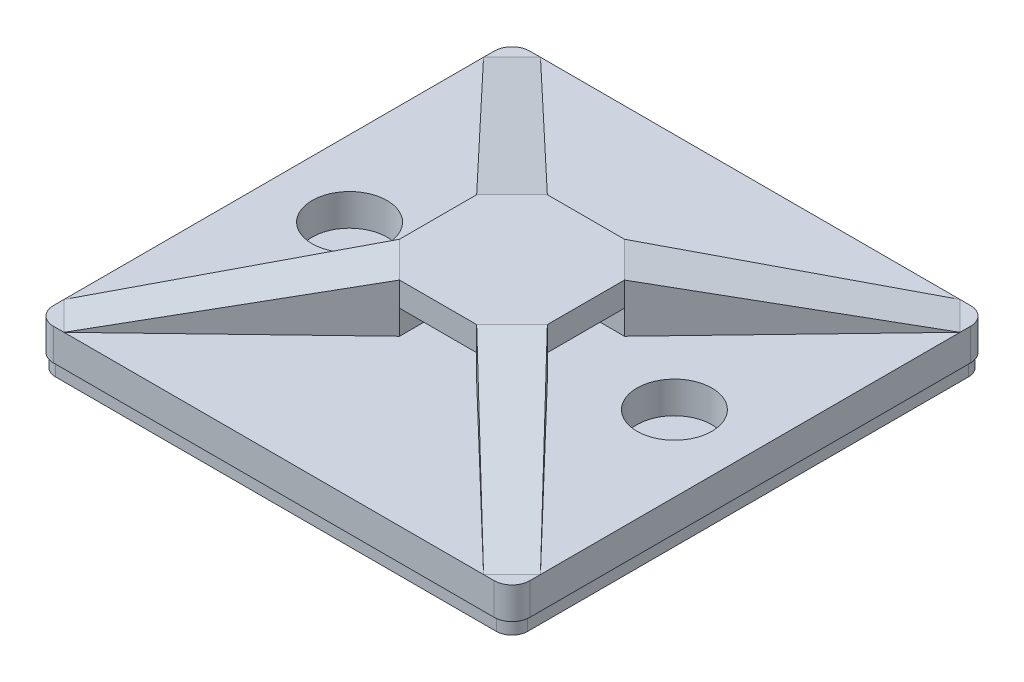
SolidWorks part; units mm, degrees
material "Nylon White"
ref_plane "Front Plane" through (0, 0, 0) normal (0, 0, 1) x (1, 0, 0)
ref_plane "Top Plane" through (0, 0, 0) normal (0, 1, 0) x (1, 0, 0)
ref_plane "Right Plane" through (0, 0, 0) normal (1, 0, 0) x (0, 0, -1)
sketch "Sketch1" plane through (0, 0, 0) normal (0, 1, 0) x (1, 0, 0)
  line L1 (13.2207, -14.2875) -> (-13.2207, -14.2875)
  line L2 (14.2875, -13.2207) -> (14.2875, 13.2207)
  line L3 (13.2207, 14.2875) -> (-13.2207, 14.2875)
  line L4 (-14.2875, -13.2207) -> (-14.2875, 13.2207)
  line L5 (14.2875, -14.2875) -> (-14.2875, 14.2875) construction
  line L6 (14.2875, 14.2875) -> (-14.2875, -14.2875) construction
  arc A0 (-14.2875, -13.2207) -> (-13.2207, -14.2875) centre (-13.2207, -13.2207) ccw
  arc A1 (14.2875, -13.2207) -> (13.2207, -14.2875) centre (13.2207, -13.2207) cw
  arc A2 (13.2207, 14.2875) -> (14.2875, 13.2207) centre (13.2207, 13.2207) cw
  arc A3 (-13.2207, 14.2875) -> (-14.2875, 13.2207) centre (-13.2207, 13.2207) ccw
  point P0 (0, 0)
  dimension "D2" = 1.0668
  dimension "D1" = 28.575
extrude "Boss-Extrude1" add sketch "Sketch1" along normal blind 1.905
sketch "Sketch2" plane through (0, 1.905, 0) normal (0, 1, 0) x (1, 0, 0)
  line L0 (-4.4323, 2.313) -> (-2.313, 4.4323) construction
  line L1 (4.4323, -2.313) -> (-4.4323, -2.313) construction
  line L2 (4.4323, -2.313) -> (4.4323, 2.313)
  line L3 (4.4323, 2.313) -> (-4.4323, 2.313) construction
  line L4 (-4.4323, -2.313) -> (-4.4323, 2.313)
  line L5 (4.4323, -2.313) -> (-4.4323, 2.313) construction
  line L6 (4.4323, 2.313) -> (-4.4323, -2.313) construction
  line L7 (2.313, -4.4323) -> (-2.313, -4.4323)
  line L8 (2.313, -4.4323) -> (2.313, 4.4323) construction
  line L9 (2.313, 4.4323) -> (-2.313, 4.4323)
  line L10 (-2.313, -4.4323) -> (-2.313, 4.4323) construction
  line L11 (2.313, -4.4323) -> (-2.313, 4.4323) construction
  line L12 (2.313, 4.4323) -> (-2.313, -4.4323) construction
  line L13 (2.313, 4.4323) -> (4.4323, 2.313) construction
  line L14 (4.4323, -2.313) -> (2.313, -4.4323) construction
  line L15 (-4.4323, -2.313) -> (-2.313, -4.4323) construction
  line L16 (-14.2875, 12.5813) -> (-12.5813, 14.2875)
  line L17 (-14.2875, 13.2207) -> (-14.2875, -13.2207) construction
  line L18 (13.2207, 14.2875) -> (-13.2207, 14.2875) construction
  line L19 (12.5813, 14.2875) -> (14.2875, 12.5813)
  line L20 (14.2875, -13.2207) -> (14.2875, 13.2207) construction
  line L21 (14.2875, -12.5813) -> (12.5813, -14.2875)
  line L22 (-13.2207, -14.2875) -> (13.2207, -14.2875) construction
  line L23 (-12.5813, -14.2875) -> (-14.2875, -12.5813)
  line L24 (-14.2875, 12.5813) -> (-4.4323, 2.313)
  line L25 (-12.5813, 14.2875) -> (-2.313, 4.4323)
  line L26 (2.313, 4.4323) -> (12.5813, 14.2875)
  line L27 (4.4323, 2.313) -> (14.2875, 12.5813)
  line L28 (4.4323, -2.313) -> (14.2875, -12.5813)
  line L29 (-4.4323, -2.313) -> (-14.2875, -12.5813)
  line L30 (-2.313, -4.4323) -> (-12.5813, -14.2875)
  line L31 (2.313, -4.4323) -> (12.5813, -14.2875)
  point P0 (0, 0)
  point P5 (0, 0)
  dimension "D1" = 8.8646
  dimension "D2" = 2.9972
  dimension "D3" = 2.413
extrude "Boss-Extrude2" add sketch "Sketch2" along normal blind 2.921
ref_axis "Axis1" through (0, 5.0673, 0) along (0, -1, 0)
ref_plane "Plane1" through (0, 0, 0) normal (0.7071, 0, 0.7071) x (0, -1, 0)
sketch "Sketch4" plane through (0, 0, 0) normal (0.7071, 0, 0.7071) x (0, -1, 0)
  line L0 (-4.826, 4.7696) -> (-1.905, 18.9991)
  line L4 (-1.905, 4.7696) -> (-1.905, 18.9991)
  line L5 (-1.905, 18.9991) -> (-4.826, 18.9991)
  line L6 (-4.826, 18.9991) -> (-4.826, 4.7696)
  line L7 (-4.826, 4.7696) -> (-1.905, 4.7696)
  line L8 (-1.905, 4.7696) -> (-1.905, 18.9991) construction
  line L9 (-1.905, 18.9991) -> (-4.826, 18.9991)
  line L10 (-4.826, 18.9991) -> (-4.826, 4.7696)
  line L11 (-4.826, 4.7696) -> (-1.905, 4.7696) construction
  dimension "D1" = 0
extrude "Cut-Extrude2" cut sketch "Sketch4" against normal through all both and the other way through all
pattern_circular "CirPattern3" count 4 every 90 about axis through (0, 5.0673, 0) along (0, -1, 0) of "Cut-Extrude2"
sketch "Sketch5" plane through (0, 0, 4.4323) normal (0, 0, 1) x (1, 0, 0)
  line L0 (-2.313, 3.3655) -> (2.313, 3.3655)
  line L1 (0, 4.826) -> (0, 3.3655) construction
  line L2 (-2.313, 4.826) -> (2.313, 4.826) construction
  line L3 (0, 3.3655) -> (0, 1.905) construction
  line L4 (-2.313, 1.905) -> (2.313, 1.905)
  line L5 (2.313, 1.905) -> (2.313, 4.826)
  line L6 (2.313, 4.826) -> (-2.313, 4.826)
  line L7 (-2.313, 4.826) -> (-2.313, 1.905)
  line L8 (-2.313, 1.905) -> (2.313, 1.905)
  line L9 (2.313, 1.905) -> (2.313, 3.3655)
  line L11 (-2.313, 3.3655) -> (-2.313, 1.905)
  dimension "D1" = 0
extrude "Cut-Extrude3" cut sketch "Sketch5" against normal through all
pattern_circular "CirPattern4" count 4 every 90 about axis through (0, 5.0673, 0) along (0, -1, 0) of "Cut-Extrude3"
hole_wizard "#8 Clearance Hole1" positions "Sketch9" profile "Sketch8" hole size "#8" standard "ANSI Inch" end condition through all
sketch "Sketch9" plane through (0, 1.905, 0) normal (0, 1, 0) x (1, 0, 0)
  line L0 (-9.7409, 0) -> (9.7409, 0) construction
  point P1 (-9.7409, 0)
  point P2 (9.7409, 0)
  dimension "D1" = 19.4818
sketch "Sketch8" plane through (-9.7409, 1.905, 0) normal (1, 0, 0) x (0, 0, 1)
  line L0 (0, 0) -> (0, 1.905)
  line L1 (0, 1.905) -> (2.2479, 1.905)
  line L2 (2.2479, 1.905) -> (2.2479, 0)
  line L5 (2.2479, 0) -> (0, 0)
  line L11 (0, -6.35) -> (0, 107.95) construction
  dimension "Thru Hole Dia." = 4.4958
  dimension "Thru Hole Depth" = 1.905
sketch "Sketch6" plane through (0, 0, 0) normal (0, -1, 0) x (1, 0, 0)
  line L0 (-14.1605, 13.2207) -> (-14.1605, -13.2207)
  line L1 (-13.2207, -14.1605) -> (13.2207, -14.1605)
  line L2 (14.1605, -13.2207) -> (14.1605, 13.2207)
  line L3 (13.2207, 14.1605) -> (-13.2207, 14.1605)
  line L4 (-14.2875, 13.2207) -> (-14.2875, -13.2207)
  line L5 (-13.2207, -14.2875) -> (13.2207, -14.2875)
  line L6 (14.2875, -13.2207) -> (14.2875, 13.2207)
  line L7 (13.2207, 14.2875) -> (-13.2207, 14.2875)
  line L8 (-14.2875, 13.2207) -> (-14.2875, -13.2207) construction
  line L9 (-13.2207, -14.2875) -> (13.2207, -14.2875) construction
  line L10 (14.2875, -13.2207) -> (14.2875, 13.2207) construction
  line L11 (13.2207, 14.2875) -> (-13.2207, 14.2875) construction
  arc A0 (-13.2207, 14.1605) -> (-14.1605, 13.2207) centre (-13.2207, 13.2207) ccw
  arc A1 (-14.1605, -13.2207) -> (-13.2207, -14.1605) centre (-13.2207, -13.2207) ccw
  arc A2 (13.2207, -14.1605) -> (14.1605, -13.2207) centre (13.2207, -13.2207) ccw
  arc A3 (14.1605, 13.2207) -> (13.2207, 14.1605) centre (13.2207, 13.2207) ccw
  arc A4 (-13.2207, 14.2875) -> (-14.2875, 13.2207) centre (-13.2207, 13.2207) ccw
  arc A5 (-14.2875, -13.2207) -> (-13.2207, -14.2875) centre (-13.2207, -13.2207) ccw
  arc A6 (13.2207, -14.2875) -> (14.2875, -13.2207) centre (13.2207, -13.2207) ccw
  arc A7 (14.2875, 13.2207) -> (13.2207, 14.2875) centre (13.2207, 13.2207) ccw
  arc A8 (-13.2207, 14.2875) -> (-14.2875, 13.2207) centre (-13.2207, 13.2207) ccw construction
  arc A9 (-14.2875, -13.2207) -> (-13.2207, -14.2875) centre (-13.2207, -13.2207) ccw construction
  arc A10 (13.2207, -14.2875) -> (14.2875, -13.2207) centre (13.2207, -13.2207) ccw construction
  arc A11 (14.2875, 13.2207) -> (13.2207, 14.2875) centre (13.2207, 13.2207) ccw construction
  dimension "D1" = 0
  dimension "D2" = 0.127
extrude "Boss-Extrude3" add sketch "Sketch6" along normal blind 0.7937
